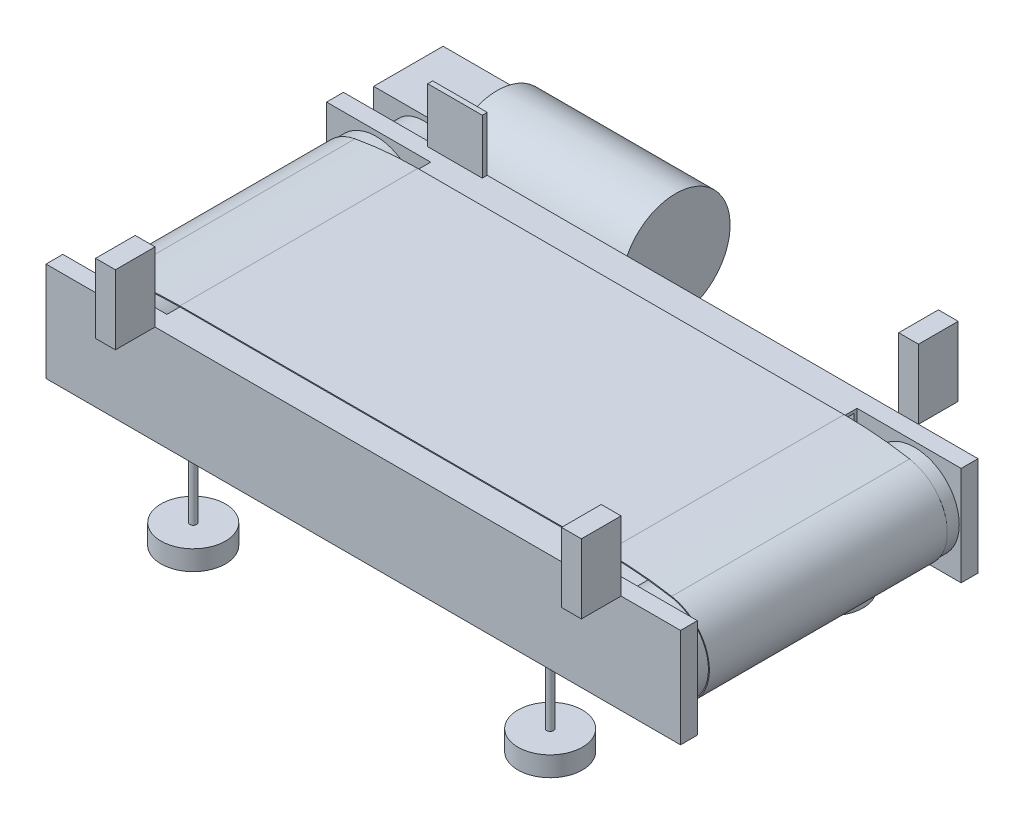
SolidWorks part; units mm, degrees
ref_plane "Alzado" through (0, 0, 0) normal (0, 0, 1) x (1, 0, 0)
ref_plane "Planta" through (0, 0, 0) normal (0, 1, 0) x (1, 0, 0)
ref_plane "Vista lateral" through (0, 0, 0) normal (1, 0, 0) x (0, 0, -1)
sketch "Croquis1" plane through (0, 0, 0) normal (0, 0, 1) x (1, 0, 0)
  line L1 (0, 0) -> (640, 0)
  line L2 (0, 0) -> (0, 100)
  line L3 (0, 100) -> (640, 100)
  line L4 (640, 0) -> (640, 100)
  dimension "D1" = 640
  dimension "D2" = 100
extrude "Saliente-Extruir1" add sketch "Croquis1" along normal mid plane 300
sketch "Croquis2" plane through (0, 100, 0) normal (0, 1, 0) x (1, 0, 0)
  line L5 (0, -150) -> (0, 150) construction
  line L6 (0, 133) -> (105, 133)
  line L7 (0, 133) -> (0, -133)
  line L8 (0, -133) -> (105, -133)
  line L9 (105, 133) -> (105, -133)
  line L10 (640, 150) -> (0, 150) construction
  line L11 (640, -150) -> (0, -150) construction
  line L12 (320, 150) -> (320, -238.7911) construction
  line L13 (535, 133) -> (535, -133)
  line L14 (640, -133) -> (535, -133)
  line L15 (640, 133) -> (640, -133)
  line L16 (640, 133) -> (535, 133)
  dimension "D1" = 17
  dimension "D2" = 17
  dimension "D3" = 105
extrude "Cortar-Extruir1" cut sketch "Croquis2" against normal mid plane 300
sketch "Croquis4" plane through (535, 0, 0) normal (1, 0, 0) x (0, 0, -1)
  line L8 (130, 3) -> (130, 97)
  line L9 (130, 97) -> (-130, 97)
  line L10 (-130, 97) -> (-130, 3)
  line L11 (-130, 3) -> (130, 3)
  line L12 (130, 3) -> (130, 97)
  line L13 (130, 97) -> (-130, 97)
  line L14 (-130, 97) -> (-130, 3)
  line L15 (-130, 3) -> (130, 3)
  dimension "D1" = 3
extrude "Cortar-Extruir2" cut sketch "Croquis4" against normal through all
sketch "Croquis5" plane through (0, 0, 0) normal (0, -1, 0) x (1, 0, 0)
  line L0 (0, 150) -> (0, 133) construction
  line L1 (0, -133) -> (0, -150) construction
  line L2 (0, -150) -> (640, -150) construction
  line L3 (320, -150) -> (320, -268.3789) construction
  circle A0 centre (140, 141.5) radius 3.5
  circle A1 centre (140, -141.5) radius 3.5
  circle A2 centre (500, -141.5) radius 3.5
  circle A3 centre (500, 141.5) radius 3.5
  point P6 (0, 141.5)
  point P7 (0, 0)
  point P11 (0, -141.5)
  dimension "D1" = 7
  dimension "D2" = 140
extrude "Saliente-Extruir2" add sketch "Croquis5" along normal blind 80
sketch "Croquis6" plane through (0, -80, 0) normal (0, -1, 0) x (1, 0, 0)
  line L0 (0, 0) -> (655.882, 0) construction
  line L1 (320, -124.3784) -> (320, -175.6216) construction
  line L2 (0, -150) -> (640, -150) construction
  circle A0 centre (500, 141.5) radius 32.5
  circle A1 centre (140, 141.5) radius 32.5
  circle A2 centre (140, -141.5) radius 32.5
  circle A3 centre (500, -141.5) radius 32.5
  point P10 (320, -150)
  dimension "D1" = 65
extrude "Saliente-Extruir3" add sketch "Croquis6" against normal blind 20 separate body
sketch "Croquis7" plane through (0, 0, -133) normal (0, 0, 1) x (1, 0, 0)
  line L0 (535, 100) -> (640, 100) construction
  circle A0 centre (593.1179, 50) radius 45
  circle A1 centre (50, 50) radius 45
  point P6 (0, 0)
  dimension "D1" = 90
  dimension "D2" = 50
  dimension "D3" = 593.1179
  dimension "D5" = 50
extrude "Saliente-Extruir4" add sketch "Croquis7" along normal up to surface (266 mm away) separate body up to face at (587.5, 50, 133)
sketch "Croquis9" plane through (0, 0, 150) normal (0, 0, 1) x (1, 0, 0)
  line L8 (105, 0) -> (535, 0)
  line L9 (105, 100) -> (535, 100)
  line L10 (105, 101) -> (535, 101)
  line L11 (105, -1) -> (535, -1)
  arc A0 (535, 100) -> (600.8679, 94.2792) centre (535, -282.0526) cw
  arc A1 (535, 0) -> (600.8679, 5.7208) centre (535, 382.0526) ccw
  arc A5 (105, 100) -> (41.8568, 94.2366) centre (105, -248.778) ccw
  arc A6 (41.8568, 94.2366) -> (41.8568, 5.7634) centre (50, 50) ccw
  arc A7 (600.8679, 5.7208) -> (600.8679, 94.2792) centre (593.1179, 50) ccw
  arc A8 (105, 0) -> (41.8568, 5.7634) centre (105, 348.778) cw
  arc A10 (601.0403, 4.7358) -> (601.0403, 95.2642) centre (593.1179, 50) ccw
  arc A11 (535, 101) -> (601.0403, 95.2642) centre (535, -282.0526) cw
  arc A12 (105, 101) -> (41.6757, 95.2201) centre (105, -248.778) ccw
  arc A13 (41.6757, 95.2201) -> (41.6757, 4.7799) centre (50, 50) ccw
  arc A14 (105, -1) -> (41.6757, 4.7799) centre (105, 348.778) cw
  arc A15 (535, -1) -> (601.0403, 4.7358) centre (535, 382.0526) ccw
  dimension "D1" = 382.0526
  dimension "D2" = 348.778
  dimension "D3" = 1
extrude "Saliente-Extruir6" add sketch "Croquis9" against normal blind 240 from offset 30 separate body offset against normal yes
sketch "Croquis11" plane through (0, 0, 150) normal (0, 0, 1) x (1, 0, 0)
  line L0 (640, 100) -> (0, 100) construction
  line L1 (560, 170) -> (580, 170)
  line L2 (560, 170) -> (560, 100)
  line L3 (560, 100) -> (580, 100)
  line L4 (580, 170) -> (580, 100)
  line L5 (640, 0) -> (640, 100) construction
  dimension "D1" = 60
  dimension "D2" = 20
  dimension "D3" = 70
extrude "Saliente-Extruir7" add sketch "Croquis11" along normal blind 40 separate body
sketch "Croquis12" plane through (0, 0, 150) normal (0, 0, 1) x (1, 0, 0)
  line L0 (640, 100) -> (0, 100) construction
  line L1 (110, 100) -> (90, 100)
  line L2 (110, 100) -> (110, 170)
  line L3 (110, 170) -> (90, 170)
  line L4 (90, 100) -> (90, 170)
  line L5 (0, 100) -> (0, 0) construction
  dimension "D1" = 110
  dimension "D2" = 20
  dimension "D3" = 70
extrude "Saliente-Extruir8" add sketch "Croquis12" along normal blind 40 separate body
mirror "Simetría4" about plane through (0, 0, 0) normal (0, 0, 1) of bodies 114
sketch "Croquis13" plane through (0, 0, 0) normal (0, 0, 1) x (1, 0, 0)
  line L0 (640, 100) -> (0, 100) construction
  line L1 (90, 100) -> (145, 100)
  line L2 (90, 100) -> (90, 155)
  line L3 (90, 155) -> (145, 155)
  line L4 (145, 100) -> (145, 155)
  dimension "D1" = 55
  dimension "D2" = 55
  dimension "D3" = 90
extrude "Saliente-Extruir9" add sketch "Croquis13" along normal blind 5 from surface starting at face at (320, 50, -150)
sketch "Croquis18" plane through (0, 0, -150) normal (0, 0, -1) x (-1, 0, 0)
  circle A0 centre (-50, 50) radius 35
  dimension "D1" = 70
extrude "Saliente-Extruir13" add sketch "Croquis18" along normal blind 60 separate body contours A0
sketch "Croquis19" plane through (0, 0, 0) normal (-1, 0, 0) x (0, 0, 1)
  line L1 (-250.5067, 90) -> (-180.5067, 90)
  line L2 (-250.5067, 90) -> (-250.5067, -5)
  line L3 (-250.5067, -5) -> (-180.5067, -5)
  line L4 (-180.5067, 90) -> (-180.5067, -5)
  dimension "D1" = 70
  dimension "D2" = 95
  dimension "D3" = 180.5067
  dimension "D4" = 5
extrude "Saliente-Extruir14" add sketch "Croquis19" against normal blind 90 separate body
sketch "Croquis20" plane through (90, 0, 0) normal (1, 0, 0) x (0, 0, -1)
  line L1 (150, 100) -> (150, 0) construction
  circle A0 centre (215, 59.0755) radius 55
  dimension "D1" = 10
  dimension "D2" = 110
  dimension "D3" = 59.0755
extrude "Saliente-Extruir15" add sketch "Croquis20" along normal blind 180 separate body
